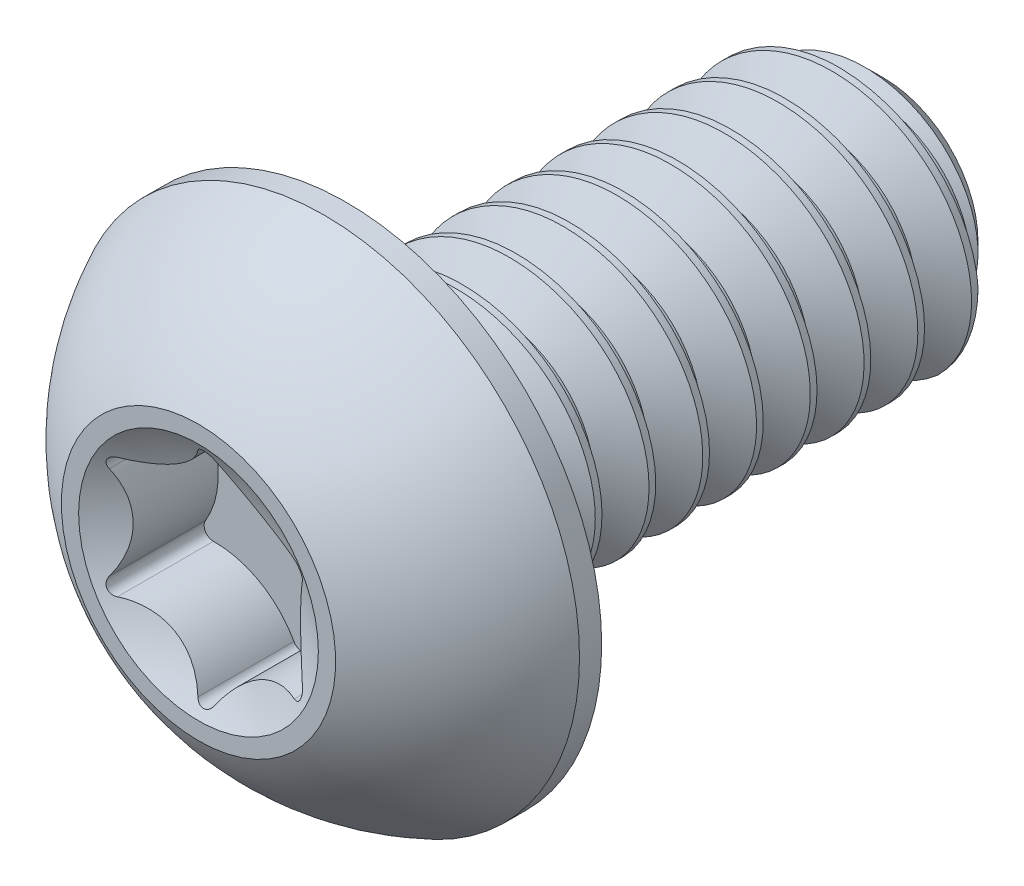
SolidWorks part; units mm, degrees
material "Plain Carbon Steel"
ref_plane "Front" through (0, 0, 0) normal (0, 0, 1) x (1, 0, 0)
ref_plane "Top" through (0, 0, 0) normal (0, 1, 0) x (1, 0, 0)
ref_plane "Right" through (0, 0, 0) normal (1, 0, 0) x (0, 0, -1)
sketch "Sketch1" plane through (0, 0, 0) normal (1, 0, 0) x (0, 0, -1)
  line L0 (0, 0) -> (5.1, 0) construction
  line L1 (0, 1.9) -> (0, 0) construction
  line L2 (1.1, 0) -> (1.1, 1.9) construction
  line L3 (5.1, 0) -> (5.1, 1) construction
  line L8 (5.0875, 1.0217) -> (5.25, 0.7402)
  line L9 (5.3, 0.7402) -> (5.4625, 1.0217)
  line L10 (5.1, 1) -> (1.1, 1) construction
  line L11 (1.1, 1.9) -> (0.935, 1.9) construction
  line L12 (5.1, 0) -> (5.1, -1) construction
  line L13 (5.075, 1.0433) -> (5.475, 1.0433) construction
  line L14 (5.475, 1.0433) -> (5.275, 0.6969) construction
  line L15 (5.275, 0.6969) -> (5.075, 1.0433) construction
  line L16 (5.275, 0.6969) -> (5.275, 0.7402) construction
  line L17 (5.275, 1.0433) -> (5.275, 1) construction
  line L18 (5.1, 1) -> (5.45, 1) construction
  line L19 (5.0875, 1.0217) -> (5.4625, 1.0217)
  line L20 (5.25, 0.7402) -> (5.3, 0.7402)
  arc A0 (0, 1.0203) -> (0.935, 1.9) centre (1.8413, 0) cw construction
  point P8 (0, 0.8303)
  point P19 (0.77, 0)
  point P21 (0, 0.6227)
  point P26 (4.1, -1)
  point P37 (5.275, 1)
  point P39 (5.275, 1.0217)
  point P42 (5.275, 0.7402)
  dimension "Head Diameter" = 3.8
  dimension "Head Height" = 1.1
  dimension "Length" = 4
  dimension "Thread Size" = 2
  dimension "Approx Drive Size " = 1.6606
  dimension "Approx Screw Head Flat" = 0.165
  dimension "Approx Drive Depth" = 0.77
  dimension "Approx Drive Gap" = 0.19
  dimension "Approx Min Drive Size" = 1.2454
  dimension "Thread Note" = 1
  dimension "Thread Pitch" = 0.4
  dimension "Pitch/8" = 0.05
sketch "Sketch2" plane through (0, 0, 0) normal (1, 0, 0) x (0, 0, -1)
  line L0 (1.1, 1.9) -> (1.1, 1) construction
  line L1 (1.1, 0) -> (1.1, 1.9) construction
  line L2 (5.1, 1) -> (1.1, 1) construction
  line L3 (1.1, 1) -> (4.8, 1)
  line L4 (5.1, 0.7) -> (5.1, 0)
  line L5 (5.1, 0) -> (1.1, 0)
  line L6 (0, 0) -> (0, 1.0203) construction
  line L7 (0.935, 1.9) -> (1.1, 1.9) construction
  line L8 (4.8, 1) -> (5.1, 0.7)
  line L9 (1.1, 1) -> (1.1, 0)
  arc A0 (0.935, 1.9) -> (0, 1.0203) centre (1.8413, 0) ccw construction
  arc A1 (0.935, 1.9) -> (0, 1.0203) centre (1.8413, 0) ccw construction
  point P11 (5.1, 1)
  dimension "D1" = 0.3
  dimension "D2" = 45
revolve "Revolve1" add sketch "Sketch2" angle 360 about L5
sketch "Sketch3" plane through (0, 0, 0) normal (1, 0, 0) x (0, 0, -1)
  line L0 (1.1, 0) -> (1.1, 1.9) construction
  line L1 (1.1, 1.9) -> (0.935, 1.9) construction
  line L2 (1.1, 0) -> (1.1, 1.9)
  line L3 (1.1, 1.9) -> (0.935, 1.9)
  line L4 (0, 1.0203) -> (0, 0)
  line L5 (0, 0) -> (1.1, 0)
  arc A0 (0.935, 1.9) -> (0, 1.0203) centre (1.8413, 0) ccw construction
  arc A1 (0.935, 1.9) -> (0, 1.0203) centre (1.8413, 0) ccw
revolve "Revolve2" add sketch "Sketch3" angle 360 about L5
combine bodies "Combine1" operation type add bodies to combine 114 109
sketch "Sketch4" plane through (0, 0, 0) normal (0, 0, 1) x (1, 0, 0)
  line L2 (0, 0) -> (-0.7191, 0.4151)
  line L3 (0, 0) -> (-1.0203, 0) construction
  line L4 (-0.6227, 0) -> (-0.6227, -0.3595) construction
  line L5 (0, 0) -> (-0.7191, -0.4151)
  line L6 (0, 0.1246) -> (-0.7191, 0.4151) construction
  circle A0 centre (0, 0) radius 0.8303 construction
  circle A1 centre (0, 0) radius 0.6227 construction
  circle A2 centre (0, 0) radius 1.9 construction
  arc A4 (-0.7185, -0.3459) -> (-0.7185, 0.3459) centre (-1.2953, 0) ccw
  arc A5 (-0.7191, 0.4151) -> (-0.7185, 0.3459) centre (-0.6599, 0.381) ccw
  arc A6 (-0.7191, -0.4151) -> (-0.7185, -0.3459) centre (-0.6599, -0.381) cw
  circle A7 centre (0, 0) radius 0.1246 construction
  circle A8 centre (0, 0) radius 1.0203 construction
  point P4 (-0.8303, 0)
  point P5 (-0.6227, 0)
  point P12 (0.7191, -0.4151)
  dimension "D4" = 0.6725
  dimension "D3" = 30
  dimension "D5" = 8
extrude "Cut-Extrude1" cut sketch "Sketch4" against normal blind 0.77
pattern_circular "CirPattern1" count 6 over 360 about axis through (0, 0, -5.1) along (0, 0, -1) of "Cut-Extrude1"
sketch "Sketch5" plane through (0, 0, 0) normal (1, 0, 0) x (0, 0, -1)
  line L0 (0, 0) -> (0.2567, 0) construction
  line L1 (-1.4215, 1.6782) -> (-1.4215, -1.6782)
  line L2 (0, 0) -> (0.1283, 0) construction
  line L3 (0, 1.0203) -> (0, -1.0203) construction
  line L4 (0, 1.0203) -> (0, 0.892) construction
  arc A0 (-1.4215, -1.6782) -> (-1.4215, 1.6782) centre (-1.4215, 0) ccw
  dimension "D1" = 0.2567
revolve "Cut-Revolve1" cut sketch "Sketch5" angle 360 about L1
split "Split1" bodies to split 113 resulting bodies 124 125 split by face at (0, 1, -1.1)
sketch "Sketch6" plane through (0, 0, -5.1) normal (0, 0, -1) x (-1, 0, 0)
  circle A0 centre (0, 0) radius 1
curve "Helix/Spiral1" pitch 0.4 height 4.4 radius 1 centre (0, 0, -5.1) axis (0, 0, 1) start towards (0, 1, 0)
sketch "Sketch7" plane through (0, 0, 0) normal (1, 0, 0) x (0, 0, -1)
  line L0 (5.0875, 1.0217) -> (5.4625, 1.0217)
  line L1 (5.4625, 1.0217) -> (5.3, 0.7402)
  line L2 (5.3, 0.7402) -> (5.25, 0.7402)
  line L3 (5.25, 0.7402) -> (5.0875, 1.0217)
sweep "Cut-Sweep1" cut profiles "Sketch7" path "Helix/Spiral1" align with end faces yes
sketch "Sketch8" plane through (0, 0, -1.1) normal (0, 0, -1) x (-1, 0, 0)
  circle A0 centre (0, 0) radius 1 construction
  circle A2 centre (0, 0) radius 1.0508
  dimension "D1" = 0.0508
extrude "Boss-Extrude1" add sketch "Sketch8" along normal up to next draft 20
equation "\"Approx Screw Head Flat@Sketch1\" = \"Head Height@Sketch1\" * .15"
equation "\"Approx Drive Depth@Sketch1\" = \"Head Height@Sketch1\" * .7"
equation "\"D1@Cut-Extrude1\" = \"Approx Drive Depth@Sketch1\""
equation "\"D1@Sketch5\" = \"Approx Drive Depth@Sketch1\" / 3"
equation "\"D1@Sketch2\" = \"Thread Pitch@Sketch1\" * .75"
equation "\"Approx Drive Gap@Sketch1\" = \"Head Diameter@Sketch1\" * .05"
equation "\"Approx Min Drive Size@Sketch1\" = \"Approx Drive Size @Sketch1\" * .75"
equation "\"Thread Note@Sketch1\" = \"Thread Pitch@Sketch1\" * 2.5"
equation "\"Pitch/8@Sketch1\" = \"Thread Pitch@Sketch1\" / 8"
equation "\"D4@Helix/Spiral1\" = \"Thread Pitch@Sketch1\""
equation "\"D3@Helix/Spiral1\" = \"Length@Sketch1\" + \"Thread Pitch@Sketch1\""
equation "\"Approx Drive Size @Sketch1\"  = \"Head Diameter@Sketch1\"*.437"
equation "\"D4@Sketch4\"=\"Approx Min Drive Size@Sketch1\"*.54"
